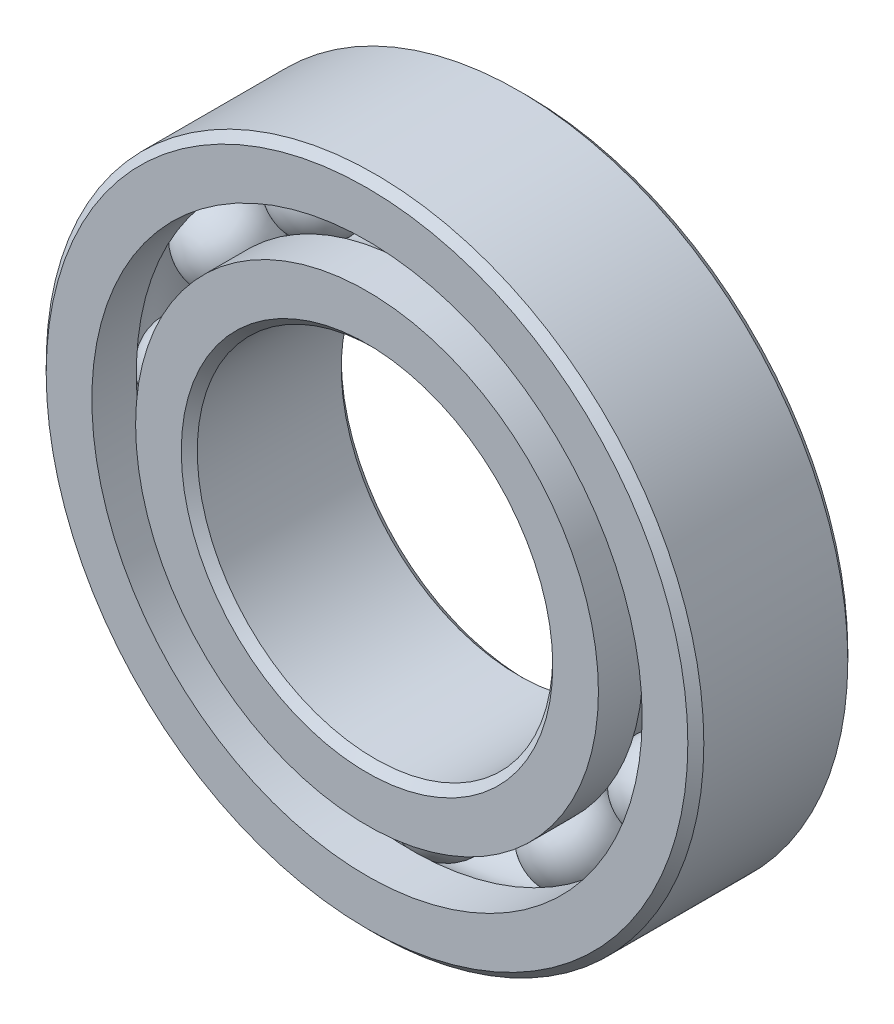
SolidWorks part; units mm, degrees
ref_plane "Front Plane" through (0, 0, 0) normal (0, 0, 1) x (1, 0, 0)
ref_plane "Top Plane" through (0, 0, 0) normal (0, 1, 0) x (1, 0, 0)
ref_plane "Right Plane" through (0, 0, 0) normal (1, 0, 0) x (0, 0, -1)
sketch "Sketch1" plane through (0, 0, 0) normal (1, 0, 0) x (0, 0, -1)
  line L0 (-4.5, 0) -> (4.5, 0) construction
  line L1 (0, 18.5) -> (0, -18.5) construction
  line L2 (4.05, 18.5) -> (-4.05, 18.5)
  line L3 (-4.05, 18.5) -> (-4.5, 18.05)
  line L4 (-4.5, 18.05) -> (-4.5, 15.4808)
  line L5 (-4.5, 15.4808) -> (-2, 15.4808)
  line L6 (4.5, 15.4808) -> (2, 15.4808)
  line L7 (4.5, 18.05) -> (4.5, 15.4808)
  line L8 (4.05, 18.5) -> (4.5, 18.05)
  line L9 (0, 18.5) -> (0, 14.25) construction
  line L10 (0, 14.25) -> (0, 10) construction
  arc A0 (-2, 15.4808) -> (2, 15.4808) centre (0, 14.25) cw
  point P14 (0, 10)
  dimension "Width" = 9
  dimension "OD" = 37
  dimension "D1" = 45
  dimension "D2" = 0.45
  dimension "Shaft Dia" = 20
  dimension "D3" = 4
  dimension "D4" = 1.2308
revolve "Revolve1" add sketch "Sketch1" angle 360 about L0
sketch "Sketch3" plane through (0, 0, 0) normal (1, 0, 0) x (0, 0, -1)
  line L0 (-4.5, 13.0192) -> (-2, 13.0192)
  line L1 (0, 18.5) -> (0, -18.5) construction
  line L2 (-4.5, 18.05) -> (-4.5, 15.4808) construction
  line L3 (-4.5, 13.0192) -> (-4.5, 10.45)
  line L4 (-4.05, 18.5) -> (-4.5, 18.05) construction
  line L5 (-4.5, 10.45) -> (-4.05, 10)
  line L6 (-4.05, 10) -> (4.05, 10)
  line L7 (4.05, 18.5) -> (4.05, -18.5) construction
  line L8 (4.05, 10) -> (4.5, 10.45)
  line L9 (4.5, -18.05) -> (4.5, 18.05) construction
  line L10 (4.5, 10.45) -> (4.5, 13.0192)
  line L11 (4.5, 13.0192) -> (2, 13.0192)
  line L13 (4.05, 18.5) -> (4.5, 18.05) construction
  arc A0 (2, 15.4808) -> (-2, 15.4808) centre (0, 14.25) ccw construction
  arc A1 (2, 13.0192) -> (-2, 13.0192) centre (0, 14.25) cw
revolve "Revolve3" add sketch "Sketch3" angle 360 about L0
sketch "Sketch4" plane through (0, 0, 0) normal (1, 0, 0) x (0, 0, -1)
  line L0 (-2.3484, 14.25) -> (2.3484, 14.25)
  arc A2 (-2.3484, 14.25) -> (2.3484, 14.25) centre (0, 14.25) cw
  arc A3 (2, 15.4808) -> (-2, 15.4808) centre (0, 14.25) ccw construction
revolve "Revolve4" add sketch "Sketch4" angle 360 about L0
ref_axis "Axis1" through (0, 0, -4.5) along (0, 0, 1)
pattern_circular "CirPattern1" count 12 every 30 about axis through (0, 0, -4.5) along (0, 0, 1) of bodies 104
sketch "Sketch5" plane through (0, 0, 0) normal (1, 0, 0) x (0, 0, -1)
  line L0 (-4.5, 15.4808) -> (-2, 15.4808) construction
  line L1 (-4.275, 15.4808) -> (-2.3484, 15.4808)
  line L2 (-4.275, 15.4808) -> (-4.275, 13.0192)
  line L3 (-4.275, 13.0192) -> (-2.3484, 13.0192)
  line L4 (-2.3484, 15.4808) -> (-2.3484, 13.0192)
  line L5 (-4.5, 13.0192) -> (-2, 13.0192) construction
  line L6 (4.5, 15.4808) -> (2, 15.4808) construction
  line L7 (4.275, 15.4808) -> (2.3484, 15.4808)
  line L8 (4.275, 15.4808) -> (4.275, 13.0192)
  line L9 (4.275, 13.0192) -> (2.3484, 13.0192)
  line L10 (2.3484, 15.4808) -> (2.3484, 13.0192)
  line L11 (4.5, 13.0192) -> (2, 13.0192) construction
  line L12 (-4.05, 18.5) -> (-4.5, 18.05) construction
  point P18 (-4.275, 18.275)
equation "\"D2@Sketch1\" = \"Width@Sketch1\"*.05"
equation "\"D3@Sketch1\" = \"Width@Sketch1\"/2.25"
equation "\"D4@Sketch1\" = (((\"OD@Sketch1\"-\"Width@Sketch1\")/2)/3.25)/3.5"
equation "\"D2@CirPattern1\" = 360/\"Balls@CirPattern1\""
